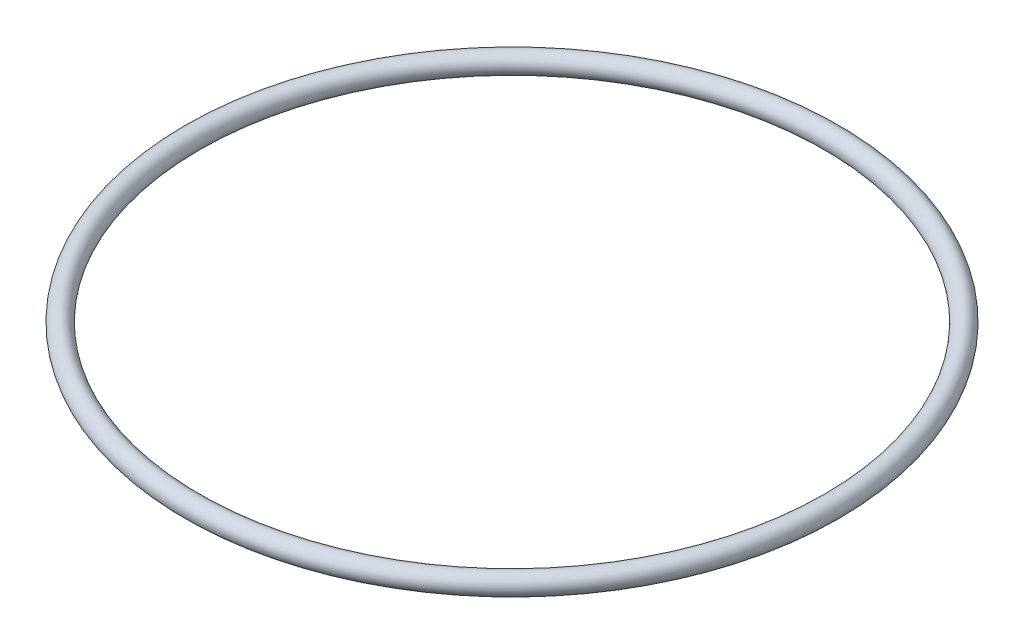
SolidWorks part; units mm, degrees
ref_plane "正面" through (0, 0, 0) normal (0, 0, 1) x (1, 0, 0)
ref_plane "平面" through (0, 0, 0) normal (0, 1, 0) x (1, 0, 0)
ref_plane "右側面" through (0, 0, 0) normal (1, 0, 0) x (0, 0, -1)
ref_axis "x軸" through (-88.99, 0, 0) along (1, 0, 0)
ref_axis "y軸" through (0, 55, 0) along (0, -1, 0)
ref_axis "z軸" through (0, 0, -88.99) along (0, 0, 1)
sketch "ｽｹｯﾁ1" plane through (0, 0, 0) normal (0, 1, 0) x (1, 0, 0)
  circle A0 centre (0, 0) radius 63.662
  point P3 (63.662, 0)
  dimension "D1" = 127.324
sketch "ｽｹｯﾁ2" plane through (0, 0, 0) normal (0, 0, 1) x (1, 0, 0)
  line L0 (63.662, 0) -> (-63.662, 0) construction
  line L1 (-88.99, 0) -> (88.99, 0) construction
  circle A0 centre (63.662, 0) radius 2
  point P6 (0, 0)
  point P7 (63.911, 0)
  point P8 (63.662, 0)
  point P9 (64.2862, 0)
  dimension "D1" = 4
sweep "ｽｲｰﾌﾟ1" add profiles "ｽｹｯﾁ2" path "ｽｹｯﾁ1"
